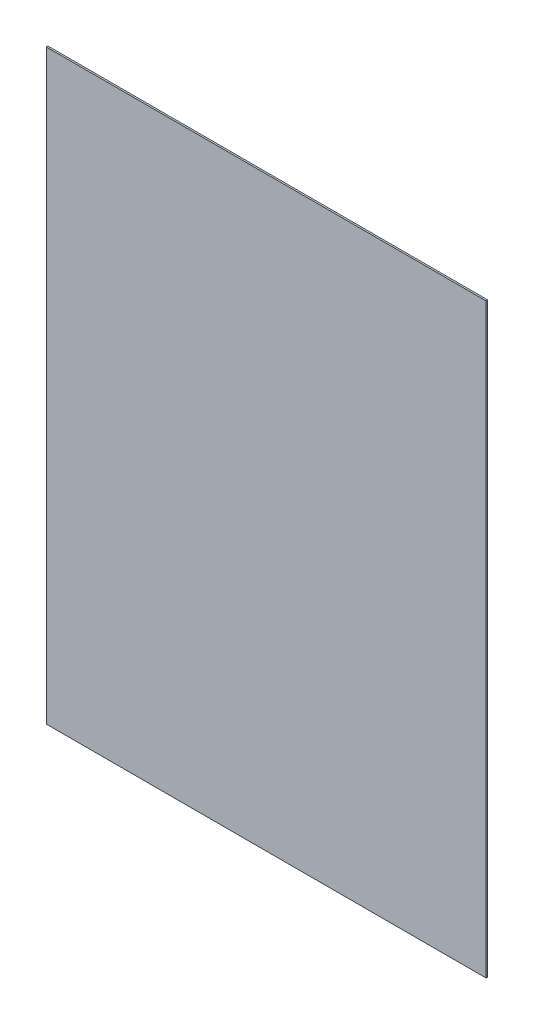
SolidWorks part; units mm, degrees
material "Acrylic (Medium-high impact)"
ref_plane "Front Plane" through (0, 0, 0) normal (0, 0, 1) x (1, 0, 0)
ref_plane "Top Plane" through (0, 0, 0) normal (0, 1, 0) x (1, 0, 0)
ref_plane "Right Plane" through (0, 0, 0) normal (1, 0, 0) x (0, 0, -1)
sketch "Sketch1" plane through (0, 0, 0) normal (0, 0, 1) x (1, 0, 0)
  line L1 (0, 0) -> (838.2, 0)
  line L2 (0, 0) -> (0, 1117.6)
  line L3 (0, 1117.6) -> (838.2, 1117.6)
  line L4 (838.2, 0) -> (838.2, 1117.6)
  dimension "D1" = 838.2
  dimension "D2" = 1117.6
extrude "Boss-Extrude1" add sketch "Sketch1" along normal blind 3.175
equation "\"L\"= 33in'length"
equation "\"W\"= 44in'width"
equation "\"t\"= 1 / 8in'thickness"
equation "\"D1@Sketch1\"=\"L\""
equation "\"D2@Sketch1\"=\"W\""
equation "\"D1@Boss-Extrude1\"=\"t\""
